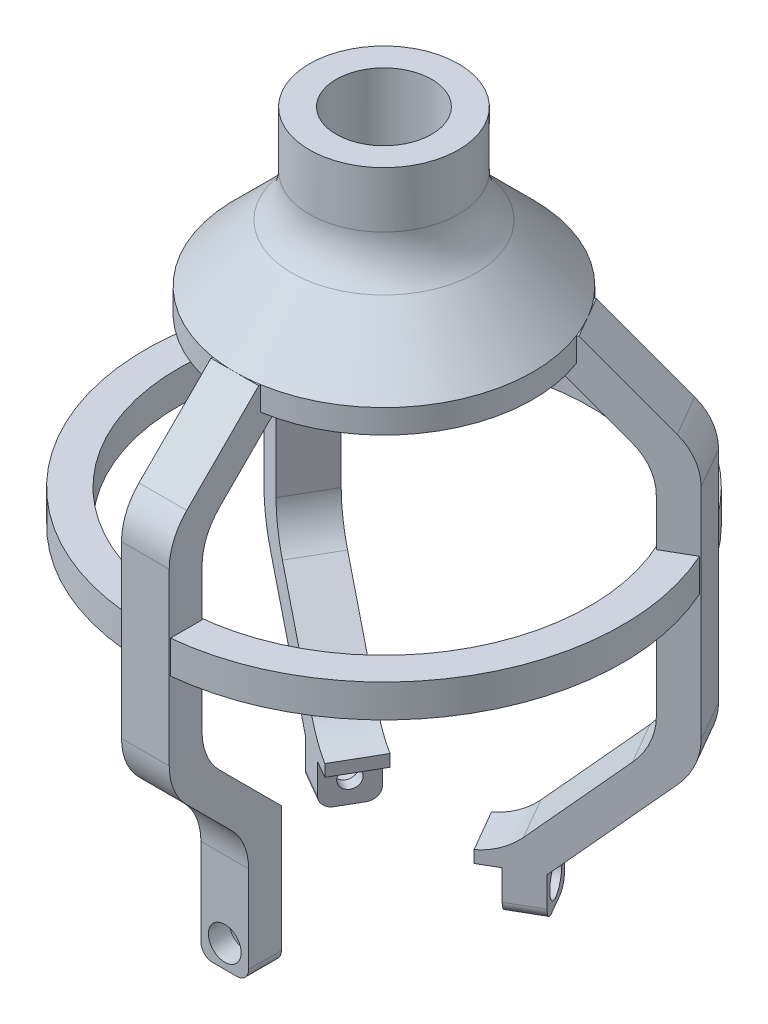
SolidWorks part; units mm, degrees
ref_plane "Piano frontale" through (0, 0, 0) normal (0, 0, 1) x (1, 0, 0)
ref_plane "Piano superiore" through (0, 0, 0) normal (0, 1, 0) x (1, 0, 0)
ref_plane "Piano destro" through (0, 0, 0) normal (1, 0, 0) x (0, 0, -1)
ref_plane "Piano1" through (-17.2567, 0, 0) normal (-1, 0, 0) x (0, 0, 1)
ref_plane "Piano2" through (15.9946, 0, 27.7035) normal (0.5, 0, 0.866) x (0.866, 0, -0.5)
ref_plane "Piano3" through (0, -4.4199, 0) normal (0, -1, 0) x (-1, 0, 0)
ref_axis "Assi1" through (-17.2567, 55, 46.9012) along (0, -1, 0)
sketch "Schizzo2" plane through (15.9946, 0, 27.7035) normal (0.5, 0, 0.866) x (0.866, 0, -0.5)
  line L0 (-22.8069, -2.8449) -> (-22.8069, -5.0199)
  line L1 (-22.8069, -5.0199) -> (-17.3069, -5.0199)
  line L2 (-17.3069, -5.0199) -> (-17.3069, 1.9801)
  line L3 (-17.3069, 1.9801) -> (1.6047, 20.8917)
  line L4 (1.6047, 20.8917) -> (1.6047, 65.8917)
  line L5 (1.6047, 65.8917) -> (-13.3953, 80.8917)
  line L7 (-17.1735, 76.8917) -> (-3.8953, 63.6135)
  line L8 (-3.8953, 63.6135) -> (-3.8953, 23.1699)
  line L9 (-3.8953, 23.1699) -> (-23.085, 3.9801)
  line L12 (-55, -4.4199) -> (55, -4.4199) construction
  line L13 (-13.3953, 80.8917) -> (-29.3953, 80.8917)
  line L14 (-29.3953, 80.8917) -> (-29.3953, 76.8917)
  line L15 (-29.3953, 76.8917) -> (-17.1735, 76.8917)
  line L16 (-23.085, 3.9801) -> (-26.2703, 3.9801)
  line L17 (-26.2703, 3.9801) -> (-26.2703, 1.9801)
  line L18 (-26.2703, 1.9801) -> (-22.8069, 1.9801)
  line L19 (-22.8069, 1.9801) -> (-22.8069, -2.8449)
  line L21 (-38.3953, 55) -> (-38.3953, -55) construction
  point P13 (-22.8069, 1.9801)
  dimension "D1" = 5.5
  dimension "D2" = 135
  dimension "D3" = 5.5
  dimension "D4" = 5.5
  dimension "D5" = 40
  dimension "D6" = 7
  dimension "D7" = 5.5
  dimension "D8" = 45
  dimension "D9" = 4
  dimension "D10" = 15
  dimension "D11" = 2
  dimension "D12" = 9
extrude "Estrusione-Estrusione2" add sketch "Schizzo2" along normal mid plane 8
sketch "Schizzo16" plane through (-14.9882, 0, 8.6534) normal (0.866, 0, -0.5) x (-0.5, 0, -0.866)
  line L0 (-27.9892, -5.0199) -> (-27.9892, 1.9801) construction
  line L1 (-35.9892, 1.9801) -> (-27.9892, 1.9801) construction
  circle A0 centre (-31.9892, -1.2199) radius 1.625
  dimension "D3" = 3.25
  dimension "D1" = 4
  dimension "D2" = 3.2
extrude "Taglio-Estrusione3" cut sketch "Schizzo16" against normal blind 7
sketch "Schizzo17" plane through (-14.9882, 0, 8.6534) normal (0.866, 0, -0.5) x (-0.5, 0, -0.866)
  circle A0 centre (-31.9892, -1.2199) radius 2.75
  dimension "D1" = 5.5
extrude "Taglio-Estrusione4" cut sketch "Schizzo17" against normal blind 3.5
fillet "Raccordo2" radius 2 2 edges at (-3.3751, -5.0199, 34.2678) (0.6249, -5.0199, 41.196)
mirror "Specchia4" about plane through (-17.2567, 0, 0) normal (-1, 0, 0) of bodies 120 104
ref_plane "Piano4" through (0, 80.8917, 0) normal (0, 1, 0) x (1, 0, 0)
sketch "Schizzo3" plane through (-17.2567, 0, 0) normal (-1, 0, 0) x (0, 0, 1)
  line L0 (68.0896, -2.8449) -> (68.0896, -5.0249)
  line L1 (68.0896, -5.0249) -> (73.5896, -5.0249)
  line L2 (73.5896, -5.0249) -> (73.5896, 15.722)
  line L3 (73.5896, 15.722) -> (86.9012, 29.0335)
  line L4 (86.9012, 29.0335) -> (86.9012, 65.8917)
  line L5 (86.9012, 65.8917) -> (71.9012, 80.8917)
  line L7 (68.123, 76.8917) -> (81.4012, 63.6135)
  line L8 (81.4012, 63.6135) -> (81.4012, 31.3117)
  line L9 (81.4012, 31.3117) -> (68.0896, 18.0001)
  line L10 (68.0896, 18.0001) -> (68.0896, -2.8449)
  line L11 (46.9012, 55) -> (46.9012, -55) construction
  line L12 (71.9012, 80.8917) -> (55.9012, 80.8917)
  line L13 (8.2105, 80.8917) -> (-8.2105, 80.8917) construction
  line L14 (55.9012, 80.8917) -> (55.9012, 76.8917)
  line L15 (55.9012, 76.8917) -> (68.123, 76.8917)
  dimension "D1" = 5.5
  dimension "D2" = 5.5
  dimension "D3" = 5.5
  dimension "D4" = 40
  dimension "D5" = 5.5
  dimension "D6" = 4
  dimension "D7" = 9
  dimension "D8" = 135
  dimension "D9" = 15
  dimension "D10" = 20.845
  dimension "D11" = 2.18
extrude "Estrusione-Estrusione3" add sketch "Schizzo3" along normal mid plane 8 separate body
sketch "Schizzo4" plane through (0, 80.8917, 0) normal (0, 1, 0) x (1, 0, 0)
  line L0 (-21.2567, -71.9012) -> (-13.2567, -71.9012) construction
  circle A0 centre (-17.2567, -46.9012) radius 25
extrude "Estrusione-Estrusione4" add sketch "Schizzo4" against normal blind 4
sketch "Schizzo5" plane through (0, 76.8917, 0) normal (0, -1, 0) x (1, 0, 0)
  circle A0 centre (-17.2567, 46.9012) radius 12.5
  dimension "D1" = 25
extrude "Estrusione-Estrusione5" add sketch "Schizzo5" against normal blind 30
sketch "Schizzo9" plane through (-17.2567, 0, 0) normal (-1, 0, 0) x (0, 0, 1)
  line L0 (46.9012, 55.2367) -> (46.9012, 124.4476) construction
  line L1 (46.9012, 55) -> (46.9012, -55) construction
  line L2 (46.9012, 80.8917) -> (71.9012, 80.8917)
  line L3 (71.9012, 80.8917) -> (46.9012, 105.8917)
  line L4 (46.9012, 105.8917) -> (46.9012, 80.8917)
  dimension "D1" = 45
revolve "Rivoluzione1" add sketch "Schizzo9" angle 360 about L0
ref_point "Punto3"
sketch "Schizzo10" plane through (-17.2567, 0, 0) normal (-1, 0, 0) x (0, 0, 1)
  line L0 (46.9012, 126.176) -> (46.9012, 54.2249) construction
  line L1 (78.1428, 66.1648) -> (46.9012, 97.4064)
  line L2 (46.9012, 66.1648) -> (78.1428, 66.1648)
  line L3 (46.9012, 97.4064) -> (46.9012, 66.1648)
  line L5 (71.9012, 80.8917) -> (59.4012, 93.3917) construction
  dimension "D1" = 6
revolve "Taglia-Rivoluzione3" cut sketch "Schizzo10" angle 360 about L0
hole_wizard "Foro Ø13.0 (13)-1" positions "Schizzo11" profile "Schizzo12" hole size "Ø13.0" standard "Ansi Metric" end condition through all
sketch "Schizzo11" plane through (0, 106.8917, 0) normal (0, 1, 0) x (1, 0, 0)
  point P0 (-17.2567, -46.9012)
sketch "Schizzo12" plane through (-17.2567, 106.8917, 46.9012) normal (1, 0, 0) x (0, 0, 1)
  line L0 (0, 0) -> (0, 111.9165)
  line L1 (0, 111.9165) -> (8, 111.9165)
  line L2 (8, 111.9165) -> (8, 0)
  line L5 (8, 0) -> (0, 0)
  line L11 (0, -6.35) -> (0, 107.95) construction
  dimension "Thru Hole Dia." = 16
  dimension "Thru Hole Depth" = 111.9165
ref_axis "Assi2" through (-17.2567, 6.1421, 46.9012) along (0, 1, 0)
ref_plane "Piano5" through (0, 48.8917, 0) normal (0, -1, 0) x (-1, 0, 0)
sketch "Schizzo13" plane through (0, 48.8917, 0) normal (0, -1, 0) x (-1, 0, 0)
  line L0 (21.2567, -86.9012) -> (13.2567, -86.9012) construction
  line L1 (-19.3843, -30.3653) -> (-15.3843, -23.437) construction
  line L2 (53.8977, -30.3653) -> (49.8977, -23.437) construction
  circle A0 centre (17.2567, -46.9012) radius 40
  circle A1 centre (17.2567, -46.9012) radius 34.5
  dimension "D1" = 5.5
extrude "Estrusione-Estrusione6" add sketch "Schizzo13" along normal mid plane 5.5
fillet "Raccordo1" radius 10 19 edges at (-17.2567, 15.722, 73.5896) (12.6212, 63.6135, 29.6512) (1.1219, 76.8917, 36.2902) (17.3843, 65.8917, 26.9012) (17.3843, 20.8917, 26.9012) (12.6212, 23.1699, 29.6512) (-17.2567, 31.3117, 81.4012) (-17.2567, 63.6135, 81.4012) (-17.2567, 29.0335, 86.9012) (-17.2567, 65.8917, 86.9012) (-47.1346, 23.1699, 29.6512) (-47.1346, 63.6135, 29.6512) (-35.6353, 76.8917, 36.2902) (-17.2567, 76.8917, 68.123) (-51.8977, 65.8917, 26.9012) (-51.8977, 20.8917, 26.9012) (-30.5158, 3.9801, 39.246) (-3.9976, 3.9801, 39.246) (-4.7567, 93.3917, 46.9012)
fillet "Raccordo3" radius 2 2 edges at (-13.2567, -5.0249, 70.8396) (-21.2567, -5.0249, 70.8396)
sketch "Schizzo18" plane through (0, 0, 73.5896) normal (0, 0, 1) x (1, 0, 0)
  line L0 (-19.2567, -5.0249) -> (-15.2567, -5.0249) construction
  line L1 (-13.2567, -3.0249) -> (-13.2567, 11.5798) construction
  circle A0 centre (-17.2567, -1.2249) radius 1.625
  dimension "D2" = 3.25
  dimension "D1" = 3.8
  dimension "D3" = 4
extrude "Taglio-Estrusione5" cut sketch "Schizzo18" against normal blind 10
sketch "Schizzo19" plane through (0, 0, 73.5896) normal (0, 0, 1) x (1, 0, 0)
  circle A0 centre (-17.2567, -1.2249) radius 2.75
  dimension "D1" = 5.5
extrude "Taglio-Estrusione6" cut sketch "Schizzo19" against normal blind 3.5
